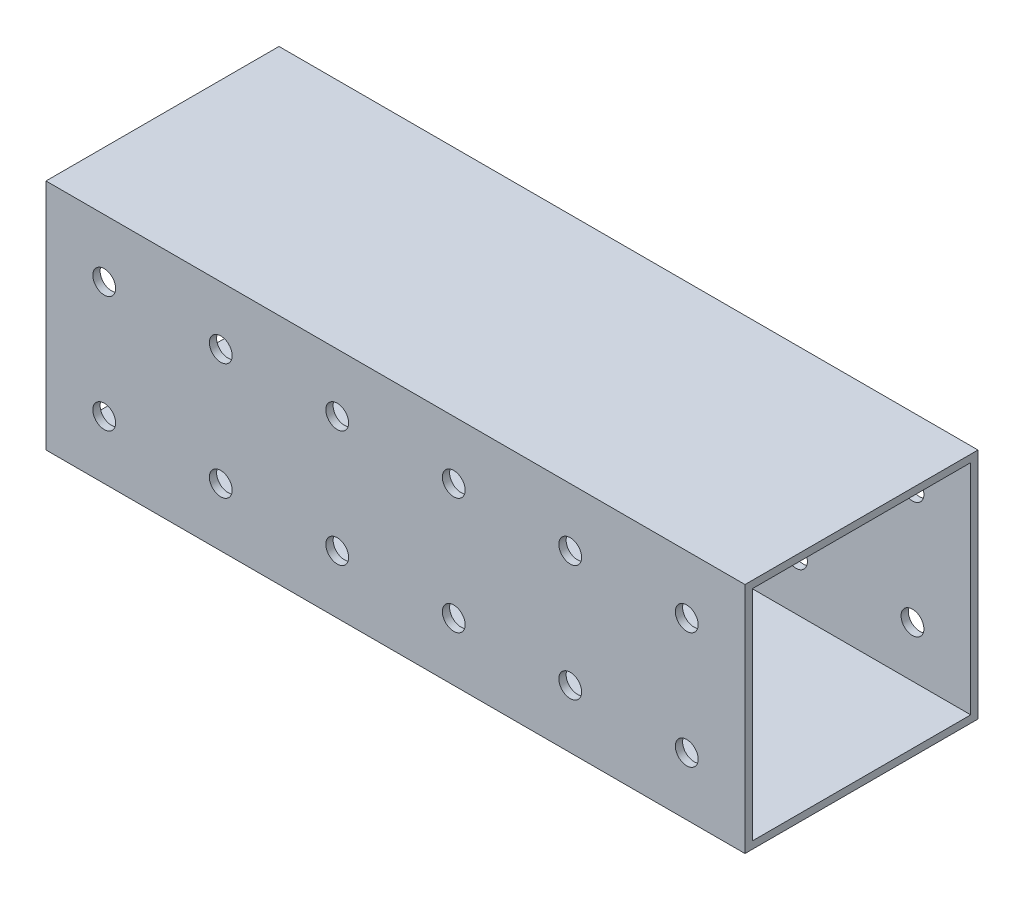
SolidWorks part; units mm, degrees
material "6061-T6 (SS)"
ref_plane "Front Plane" through (0, 0, 0) normal (0, 0, 1) x (1, 0, 0)
ref_plane "Top Plane" through (0, 0, 0) normal (0, 1, 0) x (1, 0, 0)
ref_plane "Right Plane" through (0, 0, 0) normal (1, 0, 0) x (0, 0, -1)
sketch "Sketch1" plane through (0, 0, 0) normal (1, 0, 0) x (0, 0, -1)
  line L1 (0, 0) -> (50.8, 0)
  line L2 (0, 0) -> (0, 50.8)
  line L3 (0, 50.8) -> (50.8, 50.8)
  line L4 (50.8, 0) -> (50.8, 50.8)
  dimension "D1" = 50.8
extrude "Boss-Extrude1" add sketch "Sketch1" along normal blind 152.4
shell "Shell1" thickness 1.5875 removed face at (0, 25.4, -25.4) removed face at (152.4, 25.4, -25.4)
sketch "Sketch2" plane through (0, 0, -50.8) normal (0, 0, -1) x (-1, 0, 0)
  line L0 (-152.4, 0) -> (0, 0) construction
  line L1 (0, 0) -> (0, 50.8) construction
  circle A0 centre (-12.7, 12.7) radius 2.4892
  circle A1 centre (-12.7, 38.1) radius 2.4892
  dimension "D1" = 25.4
  dimension "D3" = 12.7
  dimension "D4" = 4.9784
  dimension "D2" = 12.7
extrude "Cut-Extrude1" cut sketch "Sketch2" against normal through all
pattern_linear "LPattern1" count 6 spacing 25.4 along (1, 0, 0) of "Cut-Extrude1"
